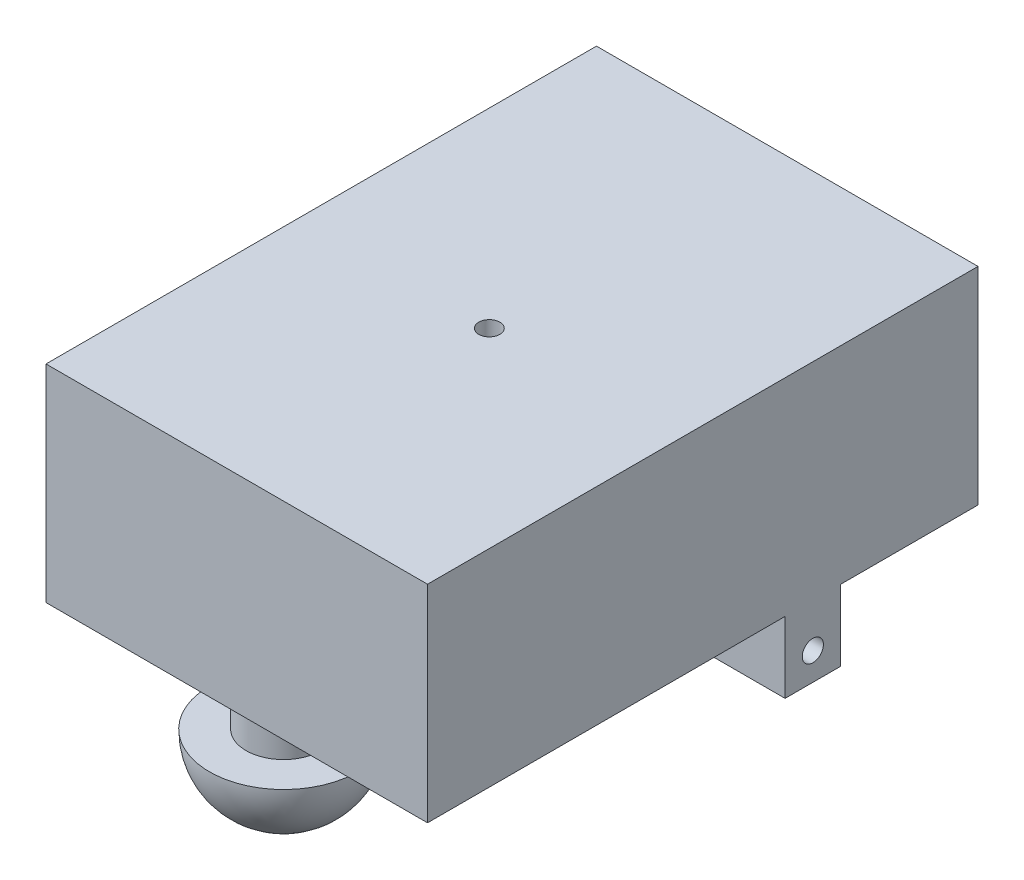
SolidWorks part; units mm, degrees
ref_plane "Front Plane" through (0, 0, 0) normal (0, 0, 1) x (1, 0, 0)
ref_plane "Top Plane" through (0, 0, 0) normal (0, 1, 0) x (1, 0, 0)
ref_plane "Right Plane" through (0, 0, 0) normal (1, 0, 0) x (0, 0, -1)
sketch "Sketch2" plane through (0, 0, 0) normal (0, 1, 0) x (1, 0, 0)
  line L1 (90, 129.855) -> (-90, 129.855)
  line L2 (90, 129.855) -> (90, -129.855)
  line L3 (90, -129.855) -> (-90, -129.855)
  line L4 (-90, 129.855) -> (-90, -129.855)
  line L5 (90, 129.855) -> (-90, -129.855) construction
  line L6 (90, -129.855) -> (-90, 129.855) construction
  point P0 (0, 0)
  dimension "D1" = 180
  dimension "D2" = 259.71
extrude "Boss-Extrude1" add sketch "Sketch2" along normal blind 97.5
sketch "Sketch3" plane through (0, 97.5, 0) normal (0, 1, 0) x (1, 0, 0)
  line L0 (0, 129.855) -> (0, -129.855) construction
  line L1 (90, 129.855) -> (-90, 129.855) construction
  line L2 (-90, -129.855) -> (90, -129.855) construction
  line L3 (-90, 0) -> (90, 0) construction
  line L4 (-90, 129.855) -> (-90, -129.855) construction
  line L5 (90, -129.855) -> (90, 129.855) construction
sketch "Sketch4" plane through (0, 0, 0) normal (0, -1, 0) x (1, 0, 0)
  line L0 (0, 129.855) -> (0, -129.855) construction
  line L1 (-90, 0) -> (90, 0) construction
  line L2 (-90, 129.855) -> (90, 129.855) construction
  line L3 (-90, 107.765) -> (90, 107.765) construction
  line L4 (-90, -129.855) -> (90, -129.855) construction
  circle A0 centre (0, 107.765) radius 17.7
  dimension "D1" = 22.09
extrude "Boss-Extrude2" add sketch "Sketch4" along normal blind 17.7
sketch "Sketch5" plane through (0, -17.7, 0) normal (0, -1, 0) x (1, 0, 0)
  circle A0 centre (0, 107.765) radius 35
extrude "Boss-Extrude3" add sketch "Sketch5" along normal blind 35
fillet "Fillet2" radius 35 1 edges at (0, -52.7, 72.765)
sketch "Sketch8" plane through (0, 0, 0) normal (0, -1, 0) x (1, 0, 0)
  line L5 (-90, -129.855) -> (90, -129.855) construction
  line L6 (-90, -51.935) -> (90, -51.935) construction
  line L7 (0, -129.855) -> (0, 129.855) construction
  line L8 (-90, -65.035) -> (90, -65.035)
  line L9 (-90, -38.835) -> (90, -38.835)
  line L10 (-90, -38.835) -> (-90, -65.035)
  line L11 (90, -38.835) -> (90, -65.035)
  dimension "D1" = 77.92
  dimension "D2" = 13.1
  dimension "D3" = 13.1
extrude "Boss-Extrude4" add sketch "Sketch8" along normal blind 33.5 contours L11 L8 L10 L9
sketch "Sketch9" plane through (90, 0, 0) normal (1, 0, 0) x (0, 0, -1)
  line L0 (129.855, 0) -> (-129.855, 0) construction
  line L1 (38.835, -33.5) -> (65.035, -33.5) construction
  line L2 (51.935, -33.5) -> (51.935, 0) construction
  line L3 (51.935, 0) -> (51.935, -20.5)
  circle A0 centre (51.935, -20.5) radius 5
extrude "Cut-Extrude1" cut sketch "Sketch9" against normal through all contours A0 region at (90, -23.9355, -48.4995)
sketch "Sketch10" plane through (0, 97.5, 0) normal (0, 1, 0) x (1, 0, 0)
  line L0 (-90, -129.855) -> (90, -129.855) construction
  line L1 (-90, -10.705) -> (90, -10.705) construction
  line L2 (0, -129.855) -> (0, 129.855) construction
  circle A0 centre (0, -10.705) radius 5
  dimension "D1" = 119.15
extrude "Cut-Extrude2" cut sketch "Sketch10" against normal blind 10
